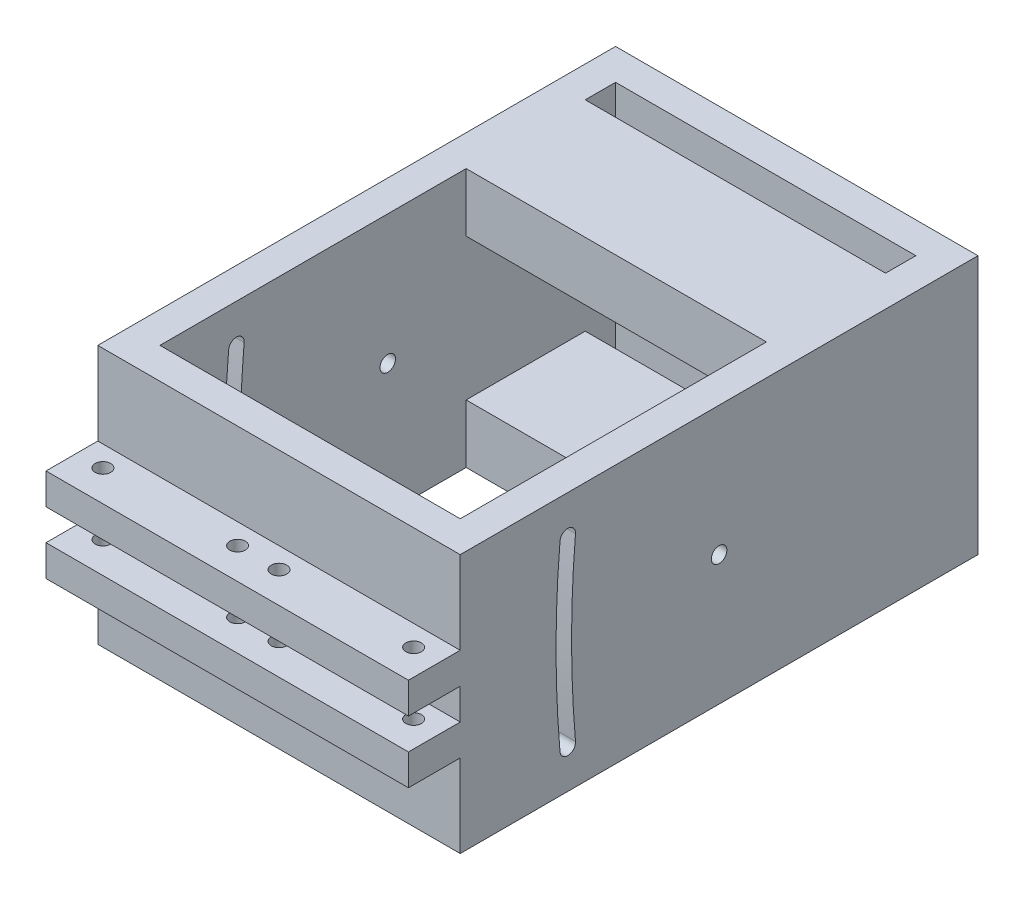
SolidWorks part; units mm, degrees
ref_plane "Front Plane" through (0, 0, 0) normal (0, 0, 1) x (1, 0, 0)
ref_plane "Top Plane" through (0, 0, 0) normal (0, 1, 0) x (1, 0, 0)
ref_plane "Right Plane" through (0, 0, 0) normal (1, 0, 0) x (0, 0, -1)
sketch "Sketch1" plane through (0, 0, 0) normal (0, 1, 0) x (1, 0, 0)
  line L1 (-35, 48.4099) -> (35, 48.4099)
  line L2 (-35, 48.4099) -> (-35, -51.5901)
  line L3 (-35, -51.5901) -> (35, -51.5901)
  line L4 (35, 48.4099) -> (35, -51.5901)
  line L14 (0, -27.5) -> (0, 27.5) construction
  line L16 (-29, 42.4099) -> (29, 42.4099)
  line L17 (-29, 42.4099) -> (-29, -45.5901)
  line L18 (-29, -45.5901) -> (29, -45.5901)
  line L19 (29, 42.4099) -> (29, -45.5901)
  point P14 (0, -51.5901)
  dimension "D1" = 70
  dimension "D2" = 100
  dimension "D3" = 6
  dimension "D4" = 6
  dimension "D5" = 6
  dimension "D6" = 6
  dimension "D9" = 0
extrude "main_body" add sketch "Sketch1" along normal blind 50
sketch "Sketch2" plane through (35, 0, 0) normal (1, 0, 0) x (0, 0, -1)
  line L0 (-51.5901, 50) -> (-51.5901, 0) construction
  circle A0 centre (-1.5901, 25) radius 1.5
  point P4 (-51.5901, 25)
  dimension "D1" = 3
  dimension "D2" = 0
  dimension "D3" = 50
sketch "Sketch3" plane through (0, 0, 51.5901) normal (0, 0, 1) x (1, 0, 0)
  line L0 (-35, 50) -> (35, 50) construction
  line L1 (35, 50) -> (35, 0) construction
  circle A0 centre (0, 25) radius 1.5
  point P4 (0, 50)
  point P7 (35, 25)
  dimension "D1" = 0
  dimension "D3" = 3
  dimension "D2" = 0
extrude "back_wire_hole" cut sketch "Sketch3" against normal up to next
sketch "Sketch6" plane through (0, 0, -48.4099) normal (0, 0, -1) x (-1, 0, 0)
  line L0 (35, 50) -> (35, 0) construction
  line L1 (-35, 50) -> (35, 50) construction
  circle A0 centre (0, 25) radius 1.5
  point P4 (35, 25)
  point P7 (0, 50)
  dimension "D1" = 0
  dimension "D3" = 3
  dimension "D2" = 0
extrude "front_wire_hole" cut sketch "Sketch6" against normal up to next
sketch "Sketch4" plane through (0, 0, 51.5901) normal (0, 0, 1) x (1, 0, 0)
  line L6 (-35, 50) -> (-35, 0) construction
  line L8 (-35, 34) -> (35, 34)
  line L10 (-35, 34) -> (-35, 28)
  line L12 (-35, 28) -> (35, 28)
  line L13 (35, 34) -> (35, 28)
  line L14 (35, 50) -> (35, 0) construction
  point P8 (-35, 25)
  dimension "D1" = 6
  dimension "D2" = 3
extrude "back_lip" add sketch "Sketch4" along normal blind 10
ref_plane "central_horizontal_plane" [suppressed] through (0, 25, 0) normal (0, 1, 0) x (1, 0, 0)
mirror "back_lip_mirror" about plane through (0, 25, 0) normal (0, 1, 0) of "back_lip"
sketch "Sketch5" plane through (0, 34, 0) normal (0, 1, 0) x (1, 0, 0)
  line L0 (35, -61.5901) -> (-35, -61.5901) construction
  line L1 (35, -51.5901) -> (-35, -51.5901) construction
  line L2 (35, -61.5901) -> (35, -51.5901) construction
  line L3 (0, -61.5901) -> (0, -51.5901) construction
  circle A0 centre (4, -55.5901) radius 1.5
  circle A1 centre (30, -55.5901) radius 1.5
  circle A2 centre (-30, -55.5901) radius 1.5
  circle A3 centre (-4, -55.5901) radius 1.5
  point P4 (0, -61.5901)
  dimension "D1" = 4
  dimension "D3" = 0
  dimension "D5" = 3
  dimension "D6" = 3
  dimension "D2" = 4
  dimension "D4" = 5
extrude "back_lip_holes" cut sketch "Sketch5" against normal through all
extrude "geared_arm_hole" cut sketch "Sketch2" against normal up to next
mirror "geared_arm_hole_mirror" about plane through (0, 0, 0) normal (1, 0, 0) of "geared_arm_hole"
sketch "alignment_sketch" plane through (35, 0, 0) normal (1, 0, 0) x (0, 0, -1)
  line L0 (-1.5901, 25) -> (48.4099, 25) construction
  line L1 (48.4099, 50) -> (48.4099, 0) construction
  line L2 (-1.5901, 25) -> (19.553, 32.6955) construction
  line L3 (-1.5901, 25) -> (19.553, 17.3045) construction
  point P5 (19.553, 32.6955)
  point P8 (19.553, 17.3045)
  dimension "D2" = 22.5
  dimension "D1" = 20
ref_axis "top_servo_alignment_axis" through (-55.368, 32.6955, -19.553) along (1, 0, 0)
ref_axis "bottom_servo_alignment_axis" through (-54.8199, 17.3045, -19.553) along (1, 0, 0)
sketch "Sketch10" plane through (-29, 0, 0) normal (1, 0, 0) x (0, 0, -1)
  line L0 (-51.5901, 0) -> (48.4099, 0) construction
  line L1 (13.553, 0) -> (36.553, 0)
  line L2 (13.553, 0) -> (13.553, 11.3045)
  line L3 (13.553, 11.3045) -> (36.553, 11.3045)
  line L4 (36.553, 0) -> (36.553, 11.3045)
  line L5 (48.4099, 25) -> (47.0508, 25) construction
  line L6 (-1.5901, 25) -> (48.4099, 25) construction
  line L7 (13.553, 38.6955) -> (36.553, 38.6955)
  line L8 (36.553, 50) -> (36.553, 38.6955)
  line L9 (13.553, 50) -> (36.553, 50)
  line L10 (13.553, 50) -> (13.553, 38.6955)
  dimension "D1" = 6
  dimension "D2" = 23
  dimension "D3" = 6
extrude "servo_mount_main_extrusion" add sketch "Sketch10" along normal up to surface (58 mm away) up to face at (29, 25, 3.0901)
sketch "Sketch11" plane through (35, 0, 0) normal (1, 0, 0) x (0, 0, -1)
  arc A0 (-30.823, 7.5) -> (-30.823, 42.5) centre (168.4099, 25) cw construction
  arc A1 (-32.3172, 42.6313) -> (-32.3172, 7.3687) centre (168.4099, 25) ccw
  arc A2 (-29.3287, 42.3688) -> (-29.3287, 7.6312) centre (168.4099, 25) ccw
  arc A3 (-29.3287, 42.3688) -> (-32.3172, 42.6313) centre (-30.823, 42.5) ccw
  arc A4 (-32.3172, 7.3687) -> (-29.3287, 7.6312) centre (-30.823, 7.5) ccw
  point P3 (-31.5901, 25)
  dimension "D1" = 1.5
  dimension "D2" = 200
  dimension "D3" = 35
  dimension "D4" = 170
extrude "wing_connection_slot" cut sketch "Sketch11" against normal up to next
mirror "wing_connection_slot_mirror" about plane through (0, 0, 0) normal (1, 0, 0) of "wing_connection_slot"
equation "\"gear_spacing\"= 22.5mm"
equation "\"D2@alignment_sketch\" = \"gear_spacing\""
equation "\"gear_angle_offset\"= 20deg"
equation "\"D1@alignment_sketch\" = \"gear_angle_offset\""
